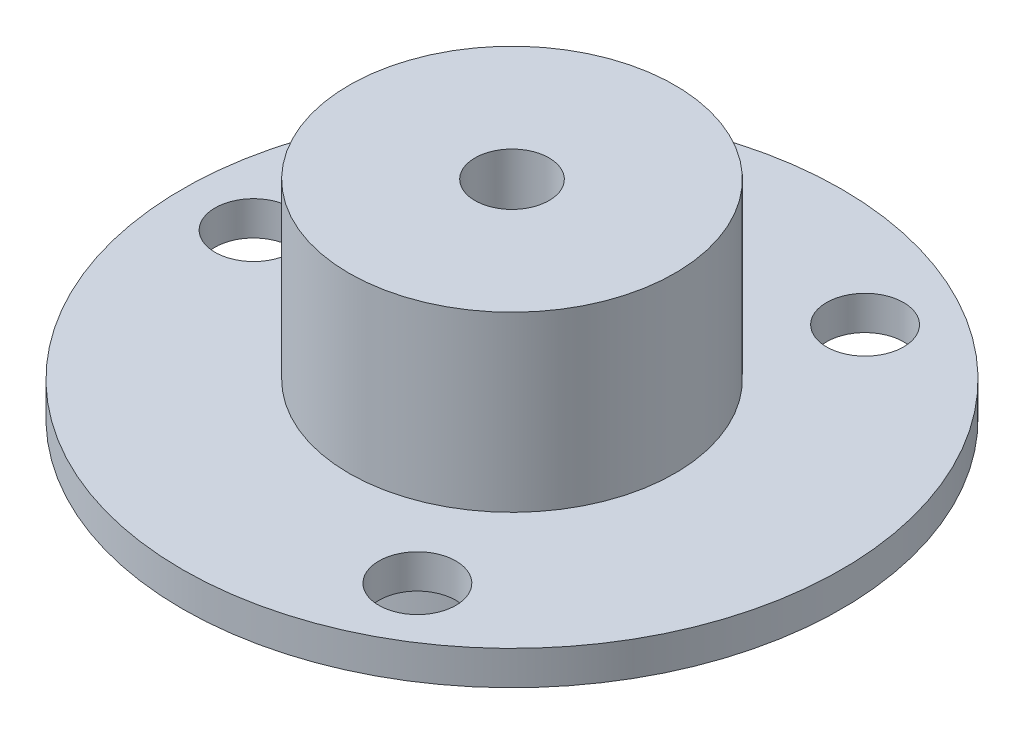
SolidWorks part; units mm, degrees
ref_plane "Front Plane" through (0, 0, 0) normal (0, 0, 1) x (1, 0, 0)
ref_plane "Top Plane" through (0, 0, 0) normal (0, 1, 0) x (1, 0, 0)
ref_plane "Right Plane" through (0, 0, 0) normal (1, 0, 0) x (0, 0, -1)
sketch "Sketch1" plane through (0, 0, 0) normal (0, 1, 0) x (1, 0, 0)
  circle A0 centre (0, 0) radius 11
  dimension "D1" = 22
extrude "Boss-Extrude1" add sketch "Sketch1" along normal blind 19
ref_plane "Plane1" through (0, 5, 0) normal (0, 1, 0) x (1, 0, 0)
sketch "Sketch2" plane through (0, 5, 0) normal (0, 1, 0) x (1, 0, 0)
  circle A0 centre (0, 0) radius 22.25
  dimension "D1" = 44.5
extrude "Boss-Extrude2" add sketch "Sketch2" along normal blind 2.3
sketch "Sketch4" plane through (0, 0, 0) normal (0, -1, 0) x (1, 0, 0)
  circle A0 centre (0, 0) radius 2.5
  dimension "D1" = 5
extrude "Cut-Extrude1" cut sketch "Sketch4" against normal through all
sketch "Sketch5" plane through (0, 5, 0) normal (0, -1, 0) x (1, 0, 0)
  line L0 (0, 0) -> (-17.45, 0) construction
  circle A1 centre (-17.45, 0) radius 2.6
  circle A2 centre (0, 0) radius 17.45 construction
  circle A3 centre (8.725, 15.1121) radius 2.6
  circle A4 centre (8.725, -15.1121) radius 2.6
  point P13 (0, 0)
  dimension "D1" = 5.2
  dimension "D2" = 34.9
  dimension "D3" = 3
extrude "Cut-Extrude2" cut sketch "Sketch5" against normal through all
sketch "Sketch6" plane through (0, 0, 0) normal (0, -1, 0) x (1, 0, 0)
  circle A0 centre (0, 0) radius 2.5 construction
  circle A1 centre (0, 0) radius 2.5
  circle A2 centre (0, 0) radius 4.5
  dimension "D1" = 9
extrude "Boss-Extrude3" add sketch "Sketch6" along normal blind 5
sketch "Sketch7" plane through (0, -5, 0) normal (0, -1, 0) x (1, 0, 0)
  line L0 (3.5, 0) -> (4.5, 0) construction
  line L1 (3.5, 0) -> (2.5, 0) construction
  line L2 (0, 0) -> (0, 1.8971) construction
  circle A0 centre (0, 0) radius 3.5 construction
  circle A2 centre (3.1035, 1.6181) radius 0.5
  circle A3 centre (3.5, 0) radius 0.5
  circle A4 centre (3.0899, -1.6439) radius 0.5
  circle A5 centre (0, 0) radius 4.5 construction
  circle A6 centre (0, 0) radius 2.5 construction
  circle A7 centre (-3.0899, -1.6439) radius 0.5
  circle A8 centre (-3.5, 0) radius 0.5
  circle A9 centre (-3.1035, 1.6181) radius 0.5
  dimension "D1" = 1
extrude "Boss-Extrude4" add sketch "Sketch7" along normal blind 3 separate body
